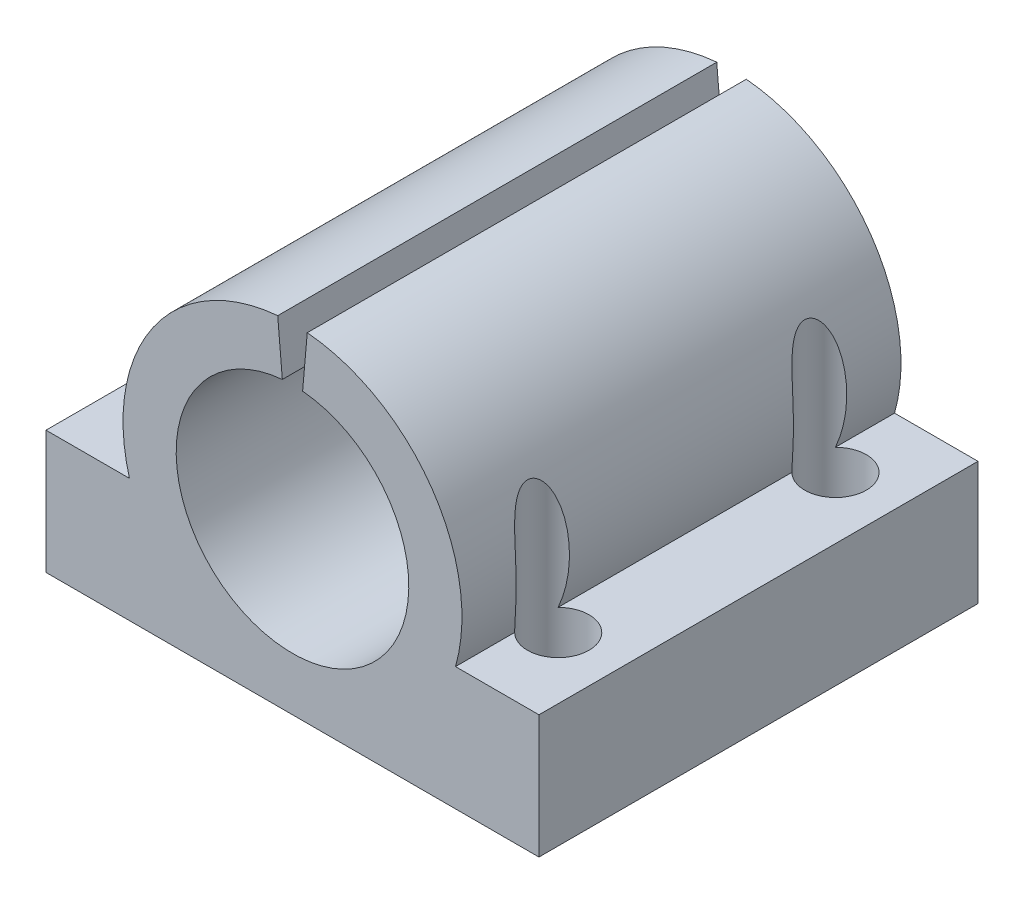
SolidWorks part; units mm, degrees
ref_plane "Front Plane" through (0, 0, 0) normal (0, 0, 1) x (1, 0, 0)
ref_plane "Top Plane" through (0, 0, 0) normal (0, 1, 0) x (1, 0, 0)
ref_plane "Right Plane" through (0, 0, 0) normal (1, 0, 0) x (0, 0, -1)
sketch "Sketch1" plane through (0, 0, 0) normal (0, 1, 0) x (1, 0, 0)
  line L1 (-16, 14.25) -> (16, 14.25)
  line L2 (-16, 14.25) -> (-16, -14.25)
  line L3 (-16, -14.25) -> (16, -14.25)
  line L4 (16, 14.25) -> (16, -14.25)
  line L5 (-16, 14.25) -> (16, -14.25) construction
  line L6 (-16, -14.25) -> (16, 14.25) construction
  point P0 (0, 0)
  dimension "D1" = 32
  dimension "D2" = 28.5
extrude "Boss-Extrude1" add sketch "Sketch1" along normal blind 8
sketch "Sketch3" plane through (0, 0, 14.25) normal (0, 0, 1) x (1, 0, 0)
  line L0 (0, 0) -> (0, 11) construction
  line L1 (-16, 0) -> (16, 0) construction
  circle A0 centre (0, 11) radius 11
  dimension "D1" = 22
  dimension "D2" = 11
extrude "Boss-Extrude2" add sketch "Sketch3" against normal through all contours A0
sketch "Sketch4" plane through (0, 0, 14.25) normal (0, 0, 1) x (1, 0, 0)
  line L0 (0, 22) -> (0, 0) construction
  arc A0 (10.583, 8) -> (-10.583, 8) centre (0, 11) ccw construction
  circle A1 centre (0, 11) radius 7.55
  dimension "D1" = 15.1
extrude "Cut-Extrude2" cut sketch "Sketch4" against normal offset from surface (26.5 mm away) 2 up to face at (0, 7.6667, -14.25)
sketch "Sketch5" plane through (0, 0, -14.25) normal (0, 0, -1) x (-1, 0, 0)
  line L0 (0, 0) -> (0, 22) construction
  arc A0 (10.583, 8) -> (-10.583, 8) centre (0, 11) ccw construction
  circle A1 centre (0, 11) radius 5
  dimension "D1" = 10
extrude "Cut-Extrude3" cut sketch "Sketch5" against normal through all
sketch "Sketch2" plane through (0, 8, 0) normal (0, 1, 0) x (1, 0, 0)
  line L0 (0, -14.25) -> (0, 14.25) construction
  line L3 (0, 0) -> (-16, 0) construction
  line L4 (-16, 14.25) -> (-16, -14.25) construction
  line L5 (-11, -14.25) -> (11, -14.25) construction
  line L6 (11, 14.25) -> (-11, 14.25) construction
  line L8 (12, 9) -> (-12, -9) construction
  line L9 (-12, 9) -> (12, -9) construction
  circle A0 centre (-12, 9) radius 2
  circle A1 centre (-12, -9) radius 2
  circle A2 centre (12, -9) radius 2
  circle A3 centre (12, 9) radius 2
  dimension "D1" = 4
  dimension "D2" = 12
  dimension "D3" = 9
  dimension "D4" = 18
  dimension "D5" = 24
  dimension "D6" = 24
  dimension "D7" = 30
extrude "Cut-Extrude1" cut sketch "Sketch2" against normal through all and the other way through all
sketch "Sketch6" plane through (0, 8, 0) normal (0, 1, 0) x (1, 0, 0)
  line L0 (-16, 0) -> (16, 0) construction
  line L1 (-16, 14.25) -> (-16, -14.25) construction
  line L2 (16, -14.25) -> (16, 14.25) construction
  line L3 (0, 14.25) -> (0, -14.25) construction
  line L4 (11, 14.25) -> (-11, 14.25) construction
  line L5 (-11, -14.25) -> (11, -14.25) construction
  line L6 (-12, 9) -> (-12, 12.2332) construction
  line L7 (-12, 12.2332) -> (-14.8, 10.6166)
  line L8 (-14.8, 10.6166) -> (-14.8, 7.3834)
  line L9 (-14.8, 7.3834) -> (-12, 5.7668)
  line L10 (-12, 5.7668) -> (-9.2, 7.3834)
  line L11 (-9.2, 7.3834) -> (-9.2, 10.6166)
  line L12 (-9.2, 10.6166) -> (-12, 12.2332)
  line L13 (-12, -9) -> (-12, -12.2332) construction
  line L14 (-9.2, -10.6166) -> (-12, -12.2332)
  line L15 (-9.2, -7.3834) -> (-9.2, -10.6166)
  line L16 (-12, -5.7668) -> (-9.2, -7.3834)
  line L17 (-14.8, -7.3834) -> (-12, -5.7668)
  line L18 (-14.8, -10.6166) -> (-14.8, -7.3834)
  line L19 (-12, -12.2332) -> (-14.8, -10.6166)
  line L20 (12, -9) -> (12, -12.2332) construction
  line L21 (12, 9) -> (12, 12.2332) construction
  line L22 (12, -12.2332) -> (14.8, -10.6166)
  line L23 (14.8, -10.6166) -> (14.8, -7.3834)
  line L24 (14.8, -7.3834) -> (12, -5.7668)
  line L25 (12, -5.7668) -> (9.2, -7.3834)
  line L26 (9.2, -7.3834) -> (9.2, -10.6166)
  line L27 (9.2, -10.6166) -> (12, -12.2332)
  line L28 (9.2, 10.6166) -> (12, 12.2332)
  line L29 (9.2, 7.3834) -> (9.2, 10.6166)
  line L30 (12, 5.7668) -> (9.2, 7.3834)
  line L31 (14.8, 7.3834) -> (12, 5.7668)
  line L32 (14.8, 10.6166) -> (14.8, 7.3834)
  line L33 (12, 12.2332) -> (14.8, 10.6166)
  circle A0 centre (-12, 9) radius 2.8 construction
  circle A1 centre (-12, -9) radius 2.8 construction
  circle A2 centre (12, -9) radius 2.8 construction
  circle A3 centre (12, 9) radius 2.8 construction
  dimension "D1" = 5.6
extrude "Cut-Extrude4" [suppressed] cut sketch "Sketch6" along normal through all and the other way blind 2.2
sketch "Sketch7" plane through (0, 0, 14.25) normal (0, 0, 1) x (1, 0, 0)
  line L0 (0, 16) -> (0, 6) construction
  line L1 (0, 11) -> (0, 22) construction
  line L2 (-0.4358, 15.981) -> (-0.9587, 21.9581)
  line L3 (0.4358, 15.981) -> (0.9587, 21.9581)
  line L4 (0, 11) -> (-0.9587, 21.9581) construction
  line L5 (0, 11) -> (0.9587, 21.9581) construction
  circle A0 centre (0, 11) radius 5 construction
  arc A1 (10.583, 8) -> (-10.583, 8) centre (0, 11) ccw construction
  arc A2 (0.9587, 21.9581) -> (-0.9587, 21.9581) centre (0, 11) ccw
  arc A3 (0.4358, 15.981) -> (-0.4358, 15.981) centre (0, 11) ccw
  dimension "D1" = 10
  dimension "D2" = 5
  dimension "D3" = 5.9772
  dimension "D4" = 5.9772
extrude "Cut-Extrude5" cut sketch "Sketch7" against normal through all
